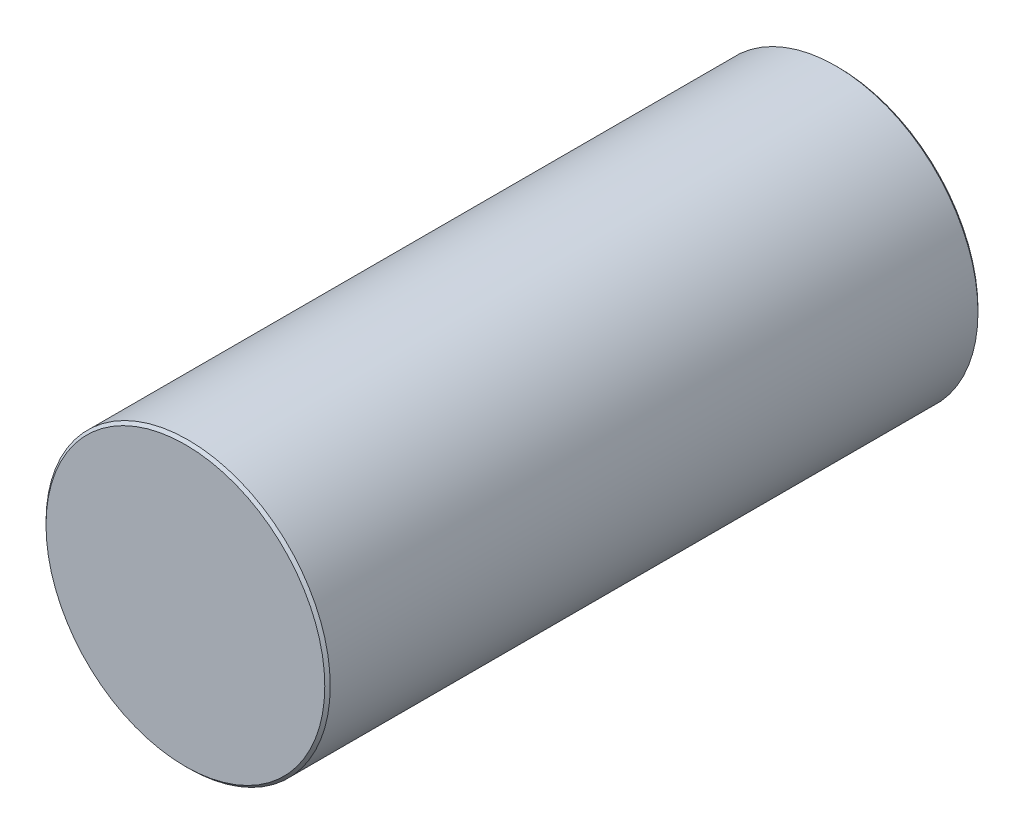
SolidWorks part; units mm, degrees
ref_plane "Front Plane" through (0, 0, 0) normal (0, 0, 1) x (1, 0, 0)
ref_plane "Top Plane" through (0, 0, 0) normal (0, 1, 0) x (1, 0, 0)
ref_plane "Right Plane" through (0, 0, 0) normal (1, 0, 0) x (0, 0, -1)
sketch "Sketch2" plane through (0, 0, 0) normal (0, 0, 1) x (1, 0, 0)
  circle A0 centre (0, 0) radius 2.6
  dimension "D1" = 5.2
extrude "Boss-Extrude1" add sketch "Sketch2" along normal blind 11.95
chamfer "Chamfer2" distance 0.05 angle 45 2 edges at (2.6, 0, 11.95) (2.6, 0, 0)
